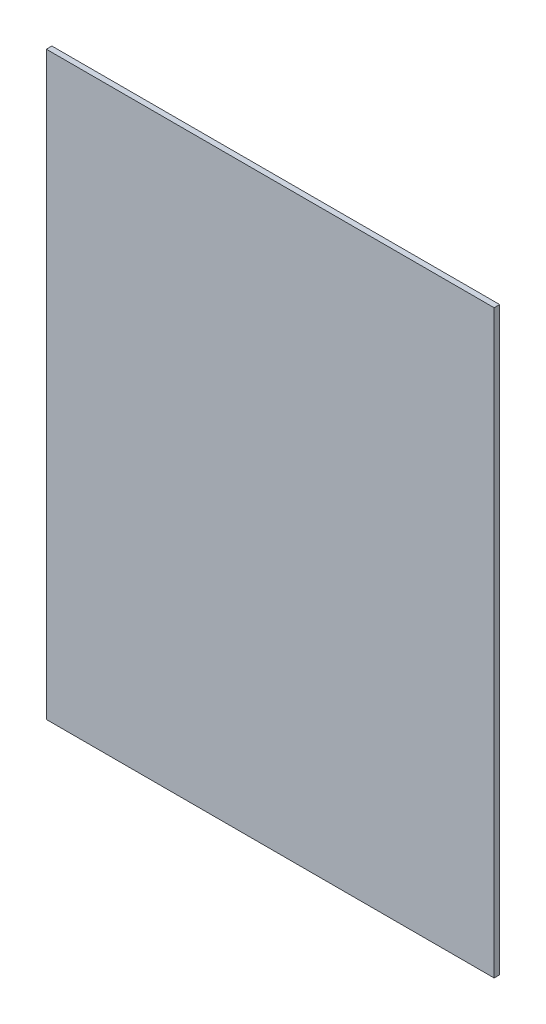
SolidWorks part; units mm, degrees
material "201 Annealed Stainless Steel (SS)"
ref_plane "Front Plane" through (0, 0, 0) normal (0, 0, 1) x (1, 0, 0)
ref_plane "Top Plane" through (0, 0, 0) normal (0, 1, 0) x (1, 0, 0)
ref_plane "Right Plane" through (0, 0, 0) normal (1, 0, 0) x (0, 0, -1)
sketch "Sketch1" plane through (0, 0, 0) normal (0, 0, 1) x (1, 0, 0)
  line L1 (-81, -105) -> (81, -105)
  line L2 (-81, -105) -> (-81, 105)
  line L3 (-81, 105) -> (81, 105)
  line L4 (81, -105) -> (81, 105)
  line L5 (-81, -105) -> (81, 105) construction
  line L6 (-81, 105) -> (81, -105) construction
  point P0 (0, 0)
  dimension "D1" = 162
  dimension "D2" = 210
extrude "Boss-Extrude1" add sketch "Sketch1" along normal blind 2
sketch "Sketch2" [suppressed] plane through (0, 0, 0) normal (0, 0, -1) x (-1, 0, 0)
  line L0 (61, 200) -> (61, -200) construction
  line L1 (-61, 314.7216) -> (-204.3993, 314.7216)
  line L2 (-61, 314.7216) -> (-61, -251.9618)
  line L3 (-61, -251.9618) -> (-204.3993, -251.9618)
  line L4 (-204.3993, 314.7216) -> (-204.3993, -251.9618)
  line L6 (61, 279.3211) -> (244.4765, 279.3211)
  line L7 (61, 279.3211) -> (61, -295.1839)
  line L8 (61, -295.1839) -> (244.4765, -295.1839)
  line L9 (244.4765, 279.3211) -> (244.4765, -295.1839)
  line L10 (-61, -200) -> (-61, -140) construction
  dimension "D1" = 122
extrude "Cut-Extrude1" [suppressed] cut sketch "Sketch2" against normal through all
sketch "Sketch3" [suppressed] plane through (0, 106, 0) normal (-1, 0, 0) x (0, 0, -1)
  line L0 (-2, -94) -> (0, -94) construction
  circle A0 centre (-7, -89) radius 2.5
  point P6 (-2, -94)
  dimension "D3" = 5
  dimension "D1" = 15
  dimension "D2" = 5
surface "Surface-Extrude1" [suppressed] sketch "Sketch3"
sketch "Sketch4" plane through (-81, 0, 0) normal (-1, 0, 0) x (0, 0, 1)
  line L1 (2, 105) -> (0, 105) construction
  line L2 (0, -105) -> (0, 105) construction
  point P0 (7.5, 101)
  dimension "D1" = 4
  dimension "D2" = 7.5
ref_axis "Axis1" through (-81, 101, 7.5) along (1, 0, 0)
sketch "Sketch5" [suppressed] plane through (0, 0, 0) normal (0, 0, -1) x (-1, 0, 0)
  line L0 (49, 80) -> (49, -80) construction
  line L1 (-49, 80) -> (49, 80)
  line L2 (-49, 80) -> (-49, 60.2594)
  line L3 (-49, 60.2594) -> (49, 60.2594)
  line L4 (49, 80) -> (49, 60.2594)
extrude "Cut-Extrude2" [suppressed] cut sketch "Sketch5" against normal blind 3
sketch "Sketch6" [suppressed] plane through (0, 0, 2) normal (0, 0, 1) x (1, 0, 0)
  line L0 (0, 0) -> (103.2002, 0) construction
  line L1 (-40, 80) -> (-40, 108.3319) construction
  line L2 (-40, 80) -> (-27.987, 80) construction
  line L3 (0, 0) -> (0, 138.3235) construction
  line L4 (40, 80) -> (27.987, 80) construction
  line L5 (40, 80) -> (40, 108.3319) construction
  line L6 (40, -80) -> (40, -108.3319) construction
  line L7 (40, -80) -> (27.987, -80) construction
  line L8 (-40, -80) -> (-27.987, -80) construction
  line L9 (-40, -80) -> (-40, -108.3319) construction
  circle A0 centre (-40, 80) radius 4.5
  circle A2 centre (-45.8, 85.8) radius 1.95
  circle A3 centre (-45.8, 74.2) radius 1.95
  circle A4 centre (-34.2, 74.2) radius 1.95
  circle A5 centre (-34.2, 85.8) radius 1.95
  circle A6 centre (34.2, 85.8) radius 1.95
  circle A7 centre (34.2, 74.2) radius 1.95
  circle A8 centre (45.8, 74.2) radius 1.95
  circle A9 centre (45.8, 85.8) radius 1.95
  circle A10 centre (40, 80) radius 4.5
  circle A11 centre (40, -80) radius 4.5
  circle A12 centre (45.8, -85.8) radius 1.95
  circle A13 centre (45.8, -74.2) radius 1.95
  circle A14 centre (34.2, -74.2) radius 1.95
  circle A15 centre (34.2, -85.8) radius 1.95
  circle A16 centre (-34.2, -85.8) radius 1.95
  circle A17 centre (-34.2, -74.2) radius 1.95
  circle A18 centre (-45.8, -74.2) radius 1.95
  circle A19 centre (-45.8, -85.8) radius 1.95
  circle A20 centre (-40, -80) radius 4.5
  circle A21 centre (-40, 80) radius 5.1 construction
  dimension "D1" = 9
  dimension "D3" = 3.9
extrude "Leandut_holes" [suppressed] cut sketch "Sketch6" against normal through all
chamfer "Chamfer1" [suppressed] distance 5 angle 45
sketch "Sketch7" plane through (0, 0, 2) normal (0, 0, 1) x (1, 0, 0)
  line L0 (81, 105) -> (-81, 105) construction
  line L1 (-31, -125) -> (31, -125)
  line L2 (-31, -125) -> (-31, 85)
  line L3 (-31, 85) -> (31, 85)
  line L4 (31, -125) -> (31, 85)
  line L5 (0, 0) -> (0, -66.8576) construction
  line L7 (-81, 105) -> (-81, -105) construction
  point P0 (0, 0)
  dimension "D1" = 20
  dimension "D2" = 50
  dimension "D3" = 62
  dimension "D4" = 125
extrude "Plunger-Window" [suppressed] cut sketch "Sketch7" against normal through all
sketch "Sketch8" [suppressed] plane through (0, 0, 2) normal (0, 0, 1) x (1, 0, 0)
  line L0 (106, 145) -> (56, 145) construction
  line L1 (-56, 125) -> (56, 125)
  line L2 (-56, 125) -> (-56, 145)
  line L3 (-56, 145) -> (56, 145)
  line L4 (56, 125) -> (56, 145)
  line L5 (56, -110) -> (56, 125) construction
extrude "Cut-Extrude3" [suppressed] cut sketch "Sketch8" against normal blind 5
sketch "Sketch9" [suppressed] plane through (0, 0, 0) normal (0, 0, -1) x (-1, 0, 0)
  line L0 (1.1, 0) -> (-1.1, 0) construction
  line L5 (6, -100) -> (-6, -100)
  line L6 (6, -100) -> (6, 5)
  line L7 (6, 5) -> (-6, 5)
  line L8 (-6, -100) -> (-6, 5)
  line L9 (-81, 25) -> (81, 25) construction
  point P0 (0, 0)
  point P8 (0, 5)
  dimension "D1" = 12
  dimension "D2" = 5
  dimension "D3" = 100
  dimension "D4" = 20
extrude "Plunger-cutout" [suppressed] cut sketch "Sketch9" against normal through all and the other way through all
sketch "Sketch10" [suppressed] plane through (0, 0, 0) normal (0, 0, -1) x (-1, 0, 0)
  line L0 (81, -147.5) -> (209.9137, 21.8916) construction
  line L1 (81, 120) -> (81, -120) construction
  line L2 (81, 120) -> (209.9137, 21.8916) construction
  line L3 (81, 120) -> (81, -147.5) construction
  line L4 (-81, 120) -> (81, 120) construction
  line L5 (-81, 120) -> (81, 120) construction
  line L6 (0, 120) -> (0, 262.0874) construction
  line L7 (-81, 120) -> (-81, -147.5)
  line L8 (-81, 120) -> (-209.9137, 21.8916)
  line L9 (-81, -147.5) -> (-209.9137, 21.8916)
  line L10 (81, 120) -> (81, -120) construction
  dimension "D1" = 147.5
  dimension "D2" = 162
  dimension "D3" = 162
  dimension "D4" = 212.8667
  dimension "D5" = 240
extrude "Boss-Extrude3" [suppressed] add sketch "Sketch10" against normal through all
sketch "Sketch11" [suppressed] plane through (0, 0, 2) normal (0, 0, 1) x (1, 0, 0)
  line L0 (81, 217.5) -> (81, -274.1687)
split line "Split Line1" [suppressed]
sketch "Sketch12" [suppressed] plane through (0, 0, 0) normal (0, 0, -1) x (-1, 0, 0)
  line L0 (81, 120) -> (81, -120) construction
  line L4 (106.722, 31) -> (106.722, -31)
  line L5 (174.722, 31) -> (106.722, 31)
  line L6 (174.722, -31) -> (174.722, 31)
  line L7 (106.722, -31) -> (174.722, -31)
  line L8 (81, 31) -> (81, -31)
  line L9 (174.722, 31) -> (81, 31)
  line L10 (174.722, -31) -> (174.722, 31)
  line L11 (81, -31) -> (174.722, -31)
  circle A0 centre (139.72, 0) radius 8
  circle A4 centre (100.7508, -22.5) radius 5 construction
  circle A5 centre (100.7508, 22.5) radius 5 construction
  circle A6 centre (100.7508, -22.5) radius 5
  circle A7 centre (100.7508, 22.5) radius 5
  dimension "D3" = 16
  dimension "D5" = 139.72
  dimension "D1" = 0
extrude "Boss-Extrude4" [suppressed] add sketch "Sketch12" against normal through all
sketch "Sketch13" [suppressed] plane through (0, 0, 0) normal (0, 0, -1) x (-1, 0, 0)
  line L0 (0, 0) -> (-166.9371, 0) construction
  line L1 (108.207, -100) -> (-114.7867, -100)
  line L2 (108.207, -100) -> (108.207, -177.524)
  line L3 (108.207, -177.524) -> (-114.7867, -177.524)
  line L4 (-114.7867, -100) -> (-114.7867, -177.524)
  line L5 (-103.1423, 100) -> (143.0141, 100)
  line L6 (-103.1423, 100) -> (-103.1423, 181.1211)
  line L7 (-103.1423, 181.1211) -> (143.0141, 181.1211)
  line L8 (143.0141, 100) -> (143.0141, 181.1211)
  dimension "D1" = 200
extrude "Cut-Extrude4" [suppressed] cut sketch "Sketch13" against normal through all
